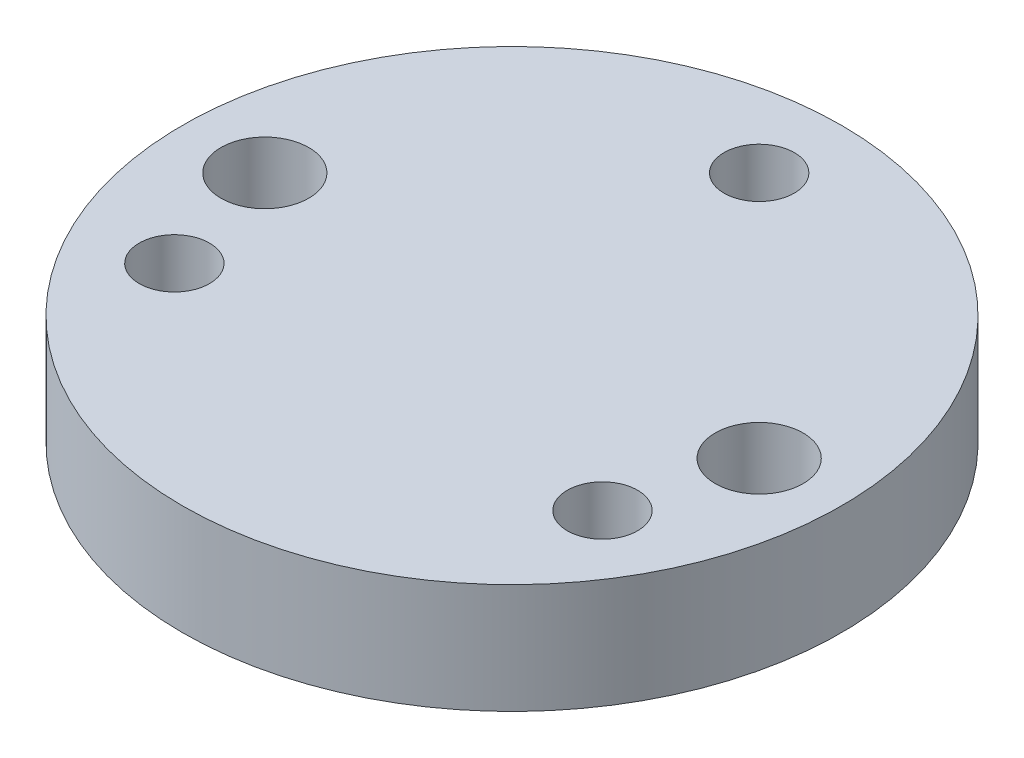
SolidWorks part; units mm, degrees
material "K110"
ref_plane "Front Plane" through (0, 0, 0) normal (0, 0, 1) x (1, 0, 0)
ref_plane "Top Plane" through (0, 0, 0) normal (0, 1, 0) x (1, 0, 0)
ref_plane "Right Plane" through (0, 0, 0) normal (1, 0, 0) x (0, 0, -1)
sketch "Sketch1" plane through (0, 0, 0) normal (0, 1, 0) x (1, 0, 0)
  circle A0 centre (0, 0) radius 30
  dimension "D1" = 60
extrude "Boss-Extrude1" add sketch "Sketch1" against normal blind 10
hole_wizard "Ø8.0mm Dowel Hole1" positions "Sketch6" profile "Sketch5" hole size "Ø8.0" standard "ISO" end condition through all
sketch "Sketch6" plane through (0, 0, 0) normal (0, 1, 0) x (1, 0, 0)
  point P0 (-22.5, 0)
  point P3 (22.5, 0)
sketch "Sketch5" plane through (-22.5, 0, 0) normal (1, 0, 0) x (0, 0, 1)
  line L0 (0, 0) -> (0, 10)
  line L1 (0, 10) -> (4, 10)
  line L2 (4, 10) -> (4, 0)
  line L5 (4, 0) -> (0, 0)
  line L11 (0, -6.35) -> (0, 107.95) construction
  dimension "Thru Hole Dia." = 8
  dimension "Thru Hole Depth" = 10
hole_wizard "M6 Clearance Hole1" positions "Sketch9" profile "Sketch8" hole size "M6" standard "ISO" end condition through all
sketch "Sketch9" plane through (0, 0, 0) normal (0, 1, 0) x (1, 0, 0)
  point P0 (19.4856, -11.25)
  point P3 (-19.4856, -11.25)
  point P6 (0, 22.5)
sketch "Sketch8" plane through (19.4856, 0, 11.25) normal (1, 0, 0) x (0, 0, 1)
  line L0 (0, 0) -> (0, 10)
  line L1 (0, 10) -> (3.2, 10)
  line L2 (3.2, 10) -> (3.2, 0)
  line L5 (3.2, 0) -> (0, 0)
  line L11 (0, -6.35) -> (0, 107.95) construction
  dimension "Thru Hole Dia." = 6.4
  dimension "Thru Hole Depth" = 10
